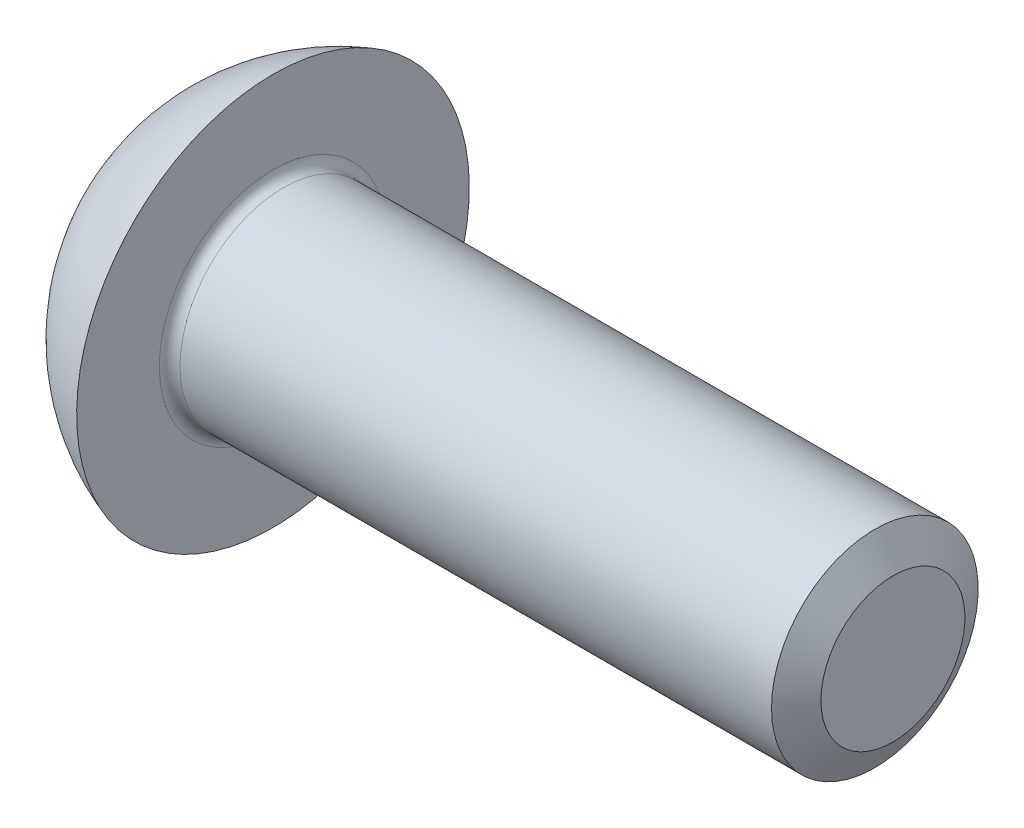
SolidWorks part; units mm, degrees
ref_plane "前视基准面" through (0, 0, 0) normal (0, 0, 1) x (1, 0, 0)
ref_plane "上视基准面" through (0, 0, 0) normal (0, 1, 0) x (1, 0, 0)
ref_plane "右视基准面" through (0, 0, 0) normal (1, 0, 0) x (0, 0, -1)
sketch "草图1" plane through (0, 0, 0) normal (0, 0, 1) x (1, 0, 0)
  line L0 (-14.2, 0) -> (0, 0) construction
  line L1 (0, 2) -> (-11.8, 2)
  line L2 (-12, 2.2) -> (-12, 3.8)
  line L3 (-14.2, 0) -> (-14.2, 2)
  line L4 (0, 2) -> (0, 0)
  line L5 (-14.2, 0) -> (0, 0)
  arc A0 (-12, 3.8) -> (-14.2, 2) centre (-10.7273, 0) ccw
  arc A1 (-11.8, 2) -> (-12, 2.2) centre (-11.8, 2.2) cw
  point P10 (-12, 2)
  dimension "r" = 0.2
  dimension "d" = 4
  dimension "dk" = 7.6
  dimension "k" = 2.2
  dimension "l" = 12
revolve "旋转1" add sketch "草图1" angle 360 about L0
cosmetic thread "装饰螺纹线1" parameters "D1"=2, "D2"=3.44
sketch "草图2" plane through (-14.2, 0, 0) normal (-1, 0, 0) x (0, 0, 1)
  line L1 (0, 1.4434) -> (-1.25, 0.7217)
  line L2 (-1.25, 0.7217) -> (-1.25, -0.7217)
  line L3 (-1.25, -0.7217) -> (0, -1.4434)
  line L4 (0, -1.4434) -> (1.25, -0.7217)
  line L5 (1.25, -0.7217) -> (1.25, 0.7217)
  line L6 (1.25, 0.7217) -> (0, 1.4434)
  circle A0 centre (0, 0) radius 1.25 construction
  dimension "s" = 2.5
extrude "切除-拉伸1" cut sketch "草图2" against normal blind 2.2
sketch "草图6" plane through (0, 0, 0) normal (0, 0, 1) x (1, 0, 0)
  line L0 (-12.9, 1.4434) -> (-12, 0)
  line L1 (-11.63, 1.4434) -> (-11.63, 0)
  line L2 (-11.63, 1.4434) -> (-12.9, 1.4434)
  line L3 (-14.2, 0) -> (-12, 0) construction
  line L4 (-11.63, 0) -> (-12, 0)
  line L5 (-14.2, 0) -> (-17.07, 0) construction
  dimension "k" = 2.2
  dimension "t" = 1.3
  dimension "e-s" = 0.37
  dimension "e" = 2.87
revolve "旋转2" add sketch "草图6" angle 360 about L3
sketch "草图7" plane through (0, 0, 0) normal (0, 0, 1) x (1, 0, 0)
  line L3 (-14.2, 1.4434) -> (-13.83, 0)
  line L4 (-14.2, 0) -> (-13.83, 0) construction
  line L7 (-14.2, 1.4434) -> (-14.2, 0)
  line L8 (-14.2, 0) -> (-13.83, 0)
  dimension "e-s" = 0.37
revolve "切除-旋转5" cut sketch "草图7" angle 360 about L4
sketch "草图4" plane through (0, 0, 0) normal (0, 0, 1) x (1, 0, 0)
  line L0 (-0.35, 2) -> (0, 1.3938)
  line L1 (-0.35, 2) -> (0.35, 2)
  line L2 (0.35, 2) -> (0, 1.3938)
  line L4 (0, -2) -> (0, 2) construction
  line L5 (-0.35, 0) -> (0.35, 0) construction
  dimension "d" = 2
  dimension "p" = 0.7
revolve "切除-旋转1" cut sketch "草图4" angle 360 about L5
ref_axis "基准轴1" through (-8.1887, 0, 0) along (1, 0, 0)
pattern_linear "阵列(线性)1" [suppressed] count 3 spacing 0.7 along (-1, 0, 0) of bodies 104
equation "\"D2@装饰螺纹线1\" = \"d@草图1\" * 0.86"
equation "\"k@草图6\" = \"k@切除-拉伸1\""
equation "\"e-s@草图6\" = \"e@草图6\" - \"s@草图2\""
equation "\"e-s@草图7\" = \"e-s@草图6\""
equation "\"d@草图4\" = \"d@草图1\" / 2"
equation "\"k@切除-拉伸1\" = \"k@草图1\""
equation "\"D1@阵列(线性)1\" = \"D1@装饰螺纹线1\" / \"p@草图4\""
equation "\"D3@阵列(线性)1\" = \"p@草图4\""
